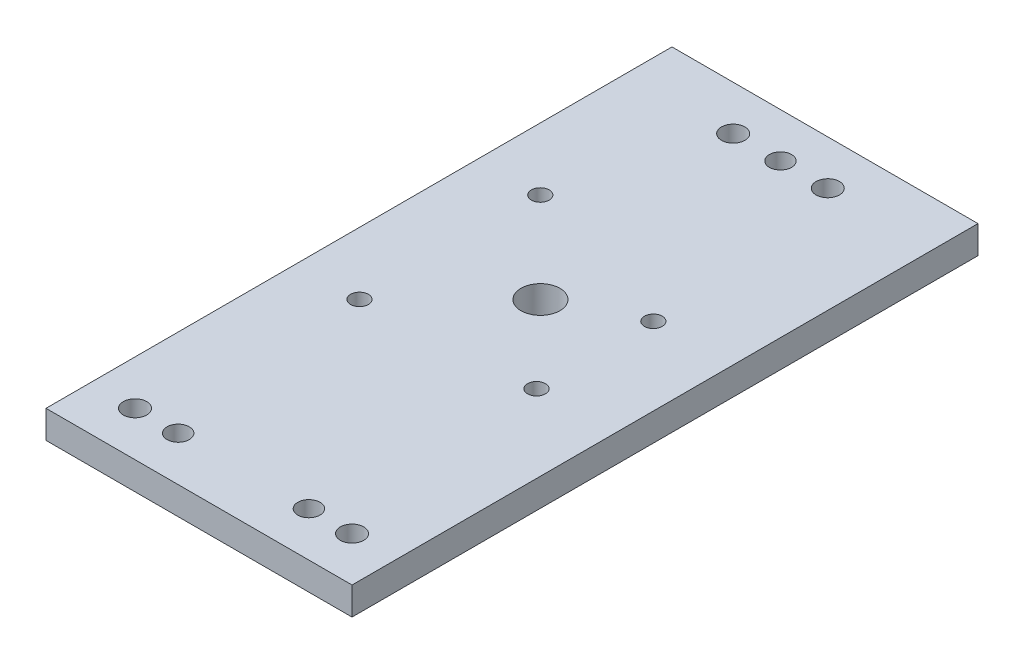
SolidWorks part; units mm, degrees
material "K110"
ref_plane "Front Plane" through (0, 0, 0) normal (0, 0, 1) x (1, 0, 0)
ref_plane "Top Plane" through (0, 0, 0) normal (0, 1, 0) x (1, 0, 0)
ref_plane "Right Plane" through (0, 0, 0) normal (1, 0, 0) x (0, 0, -1)
sketch "Sketch1" plane through (0, 0, 0) normal (0, 1, 0) x (1, 0, 0)
  line L1 (-55, -112.5) -> (55, -112.5)
  line L2 (-55, -112.5) -> (-55, 112.5)
  line L3 (-55, 112.5) -> (55, 112.5)
  line L4 (55, -112.5) -> (55, 112.5)
  line L5 (-55, -112.5) -> (55, 112.5) construction
  line L6 (-55, 112.5) -> (55, -112.5) construction
  point P0 (0, 0)
  dimension "D1" = 225
  dimension "D2" = 110
extrude "Boss-Extrude1" add sketch "Sketch1" against normal blind 10
hole_wizard "M8 Clearance Hole1" positions "Sketch4" profile "Sketch3" hole size "M8" standard "ISO" end condition through all
sketch "Sketch4" plane through (0, 0, 0) normal (0, 1, 0) x (1, 0, 0)
  point P0 (-17, 96.5)
  point P3 (17, 96.5)
  point P6 (-39, -96.5)
  point P9 (39, -96.5)
sketch "Sketch3" plane through (-17, 0, -96.5) normal (1, 0, 0) x (0, 0, 1)
  line L0 (0, 0) -> (0, 10)
  line L1 (0, 10) -> (4.2, 10)
  line L2 (4.2, 10) -> (4.2, 0)
  line L5 (4.2, 0) -> (0, 0)
  line L11 (0, -6.35) -> (0, 107.95) construction
  dimension "Thru Hole Dia." = 8.4
  dimension "Thru Hole Depth" = 10
hole_wizard "Ø8.0mm Dowel Hole1" positions "Sketch7" profile "Sketch6" hole size "Ø8.0" standard "ISO" end condition through all
sketch "Sketch7" plane through (0, 0, 0) normal (0, 1, 0) x (1, 0, 0)
  point P0 (0, 96.5)
  point P3 (-23.5, -96.5)
  point P6 (23.5, -96.5)
sketch "Sketch6" plane through (0, 0, -96.5) normal (1, 0, 0) x (0, 0, 1)
  line L0 (0, 0) -> (0, 10)
  line L1 (0, 10) -> (4, 10)
  line L2 (4, 10) -> (4, 0)
  line L5 (4, 0) -> (0, 0)
  line L11 (0, -6.35) -> (0, 107.95) construction
  dimension "Thru Hole Dia." = 8
  dimension "Thru Hole Depth" = 10
sketch "Sketch8" plane through (0, 0, 0) normal (0, 1, 0) x (1, 0, 0)
  circle A0 centre (0, 10.23) radius 7
  dimension "D1" = 14
extrude "Cut-Extrude1" cut sketch "Sketch8" against normal up to next
hole_wizard "M6 Clearance Hole1" positions "Sketch12" profile "Sketch10" hole size "M6" standard "ISO" end condition through all
sketch "Sketch12" plane through (0, 0, 0) normal (0, 1, 0) x (1, 0, 0)
  point P6 (27.065, 23.73)
  point P9 (27.065, -18.27)
  point P16 (-32.56, 42.73)
  point P19 (-32.56, -22.27)
sketch "Sketch10" plane through (27.065, 0, -23.73) normal (1, 0, 0) x (0, 0, 1)
  line L0 (0, 0) -> (0, 10)
  line L1 (0, 10) -> (3.2, 10)
  line L2 (3.2, 10) -> (3.2, 0)
  line L5 (3.2, 0) -> (0, 0)
  line L11 (0, -6.35) -> (0, 107.95) construction
  dimension "Thru Hole Dia." = 6.4
  dimension "Thru Hole Depth" = 10
